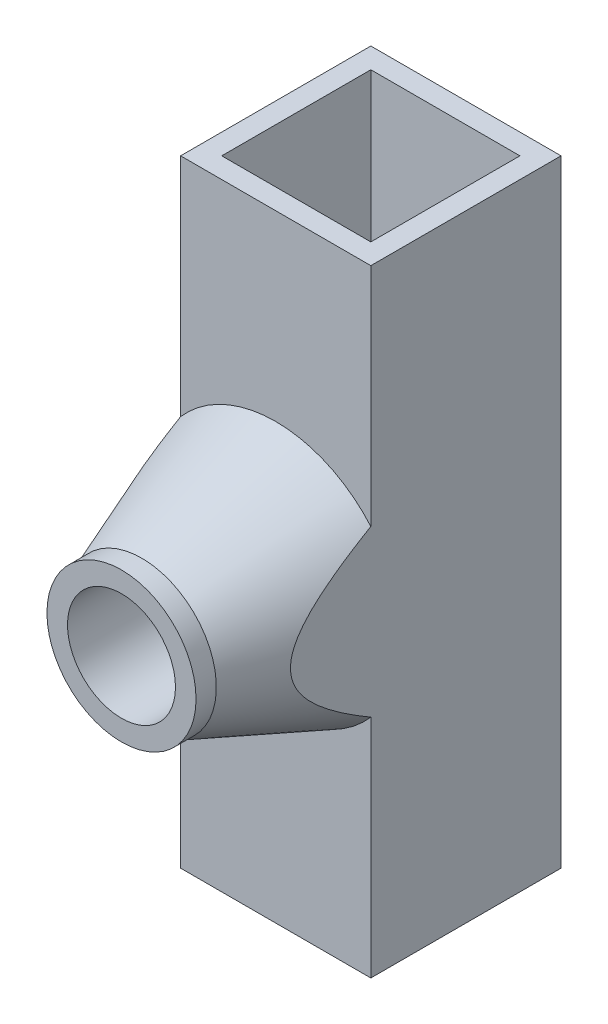
SolidWorks part; units mm, degrees
material "ABS"
ref_plane "Front Plane" through (0, 0, 0) normal (0, 0, 1) x (1, 0, 0)
ref_plane "Top Plane" through (0, 0, 0) normal (0, 1, 0) x (1, 0, 0)
ref_plane "Right Plane" through (0, 0, 0) normal (1, 0, 0) x (0, 0, -1)
sketch "Sketch1" plane through (0, 0, 0) normal (0, 1, 0) x (1, 0, 0)
  line L0 (-9.25, 9.25) -> (9.25, 9.25)
  line L1 (-7.25, -7.25) -> (7.25, -7.25)
  line L2 (-7.25, -7.25) -> (-7.25, 7.25)
  line L3 (-7.25, 7.25) -> (7.25, 7.25)
  line L4 (7.25, -7.25) -> (7.25, 7.25)
  line L5 (-7.25, -7.25) -> (7.25, 7.25) construction
  line L6 (-7.25, 7.25) -> (7.25, -7.25) construction
  line L7 (9.25, -9.25) -> (9.25, 9.25)
  line L8 (-9.25, -9.25) -> (9.25, -9.25)
  line L9 (-9.25, -9.25) -> (-9.25, 9.25)
  point P0 (0, 0)
  dimension "D1" = 14.5
  dimension "D2" = 14.5
  dimension "D3" = 2
extrude "Boss-Extrude1" add sketch "Sketch1" along normal blind 60
sketch "Sketch2" plane through (0, 0, 9.25) normal (0, 0, 1) x (1, 0, 0)
  line L0 (9.25, 60) -> (9.25, 0) construction
  circle A0 centre (0, 30) radius 5.25
  circle A1 centre (0, 30) radius 7.25
  point P4 (9.25, 30)
  point P7 (0, 0)
  dimension "D1" = 10.5
  dimension "D2" = 2
extrude "Boss-Extrude2" add sketch "Sketch2" along normal blind 15
chamfer "Chamfer1" distance 5 angle 69 1 edges at (-7.25, 30, 9.25) first distance on face at (-7.25, 30, 9.25)
